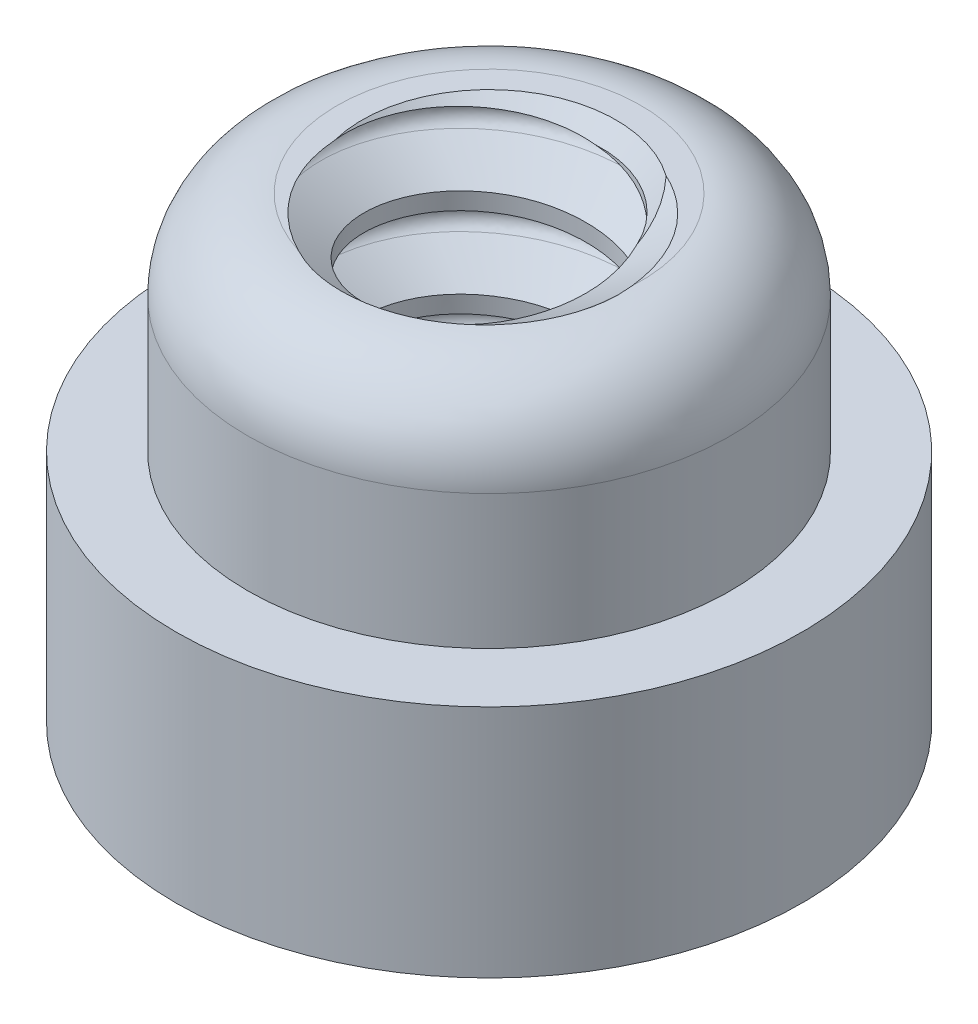
SolidWorks part; units mm, degrees
ref_plane "Ebene vorne" through (0, 0, 0) normal (0, 0, 1) x (1, 0, 0)
ref_plane "Ebene oben" through (0, 0, 0) normal (0, 1, 0) x (1, 0, 0)
ref_plane "Ebene rechts" through (0, 0, 0) normal (1, 0, 0) x (0, 0, -1)
sketch "Skizze1" plane through (0, 0, 0) normal (0, 0, 1) x (1, 0, 0)
  line L0 (0, 12.4554) -> (0, -10.8804) construction
  line L1 (7, 0) -> (2.5, 0)
  line L2 (7, 0) -> (7, 5.25)
  line L3 (7, 5.25) -> (5.4, 5.25)
  line L4 (5.4, 5.25) -> (5.4, 8.25)
  line L5 (3.4, 10.25) -> (2.5, 10.25)
  line L7 (2.5, 10.25) -> (2.5, 0)
  arc A0 (3.4, 10.25) -> (5.4, 8.25) centre (3.4, 8.25) cw
  dimension "D3" = 2
  dimension "D1" = 5.25
  dimension "D2" = 10.25
  dimension "D4" = 10.8
  dimension "D5" = 5
  dimension "D6" = 14
revolve "Rotation1" add sketch "Skizze1" angle 360 about L0
sketch "Skizze2" plane through (0, 10.25, 0) normal (0, 1, 0) x (1, 0, 0)
  circle A0 centre (0, 0) radius 2.5
curve "Spirale/Helix1" pitch 2 height 16 radius 2.5 centre (0, 10.25, 0) axis (0, -1, 0) start towards (0, 0, 1)
sketch "Skizze3" plane through (0, 0, 0) normal (1, 0, 0) x (0, 0, -1)
  line L0 (0, 0) -> (0, 16.5592) construction
  line L1 (2.5, 11.8666) -> (3.45, 11.3181)
  line L2 (3.45, 10.7985) -> (2.5, 10.25)
  line L3 (2.5, 10.25) -> (2.5, 11.8666)
  line L4 (2.5, 10.25) -> (-2.5, 10.25) construction
  arc A0 (3.45, 11.3181) -> (3.45, 10.7985) centre (3.3, 11.0583) cw
  point P10 (0, 0)
  dimension "D2" = 0.3
  dimension "D1" = 60
  dimension "D3" = 5
  dimension "D4" = 3.6
sweep "Schnitt-Austragung2" cut profiles "Skizze3" path "Spirale/Helix1"
sketch "Skizze4" plane through (0, 0, 0) normal (1, 0, 0) x (0, 0, -1)
  line L0 (3.5257, 10.9873) -> (1.5624, 8.875)
  line L1 (1.5624, 8.875) -> (0, 8.875)
  line L2 (0, 8.875) -> (0, 10.9873)
  line L3 (0, 10.9873) -> (3.5257, 10.9873)
  line L4 (0, 0) -> (0, 11.2369) construction
revolve "Schnitt-Rotation1" cut sketch "Skizze4" angle 360 about L4
